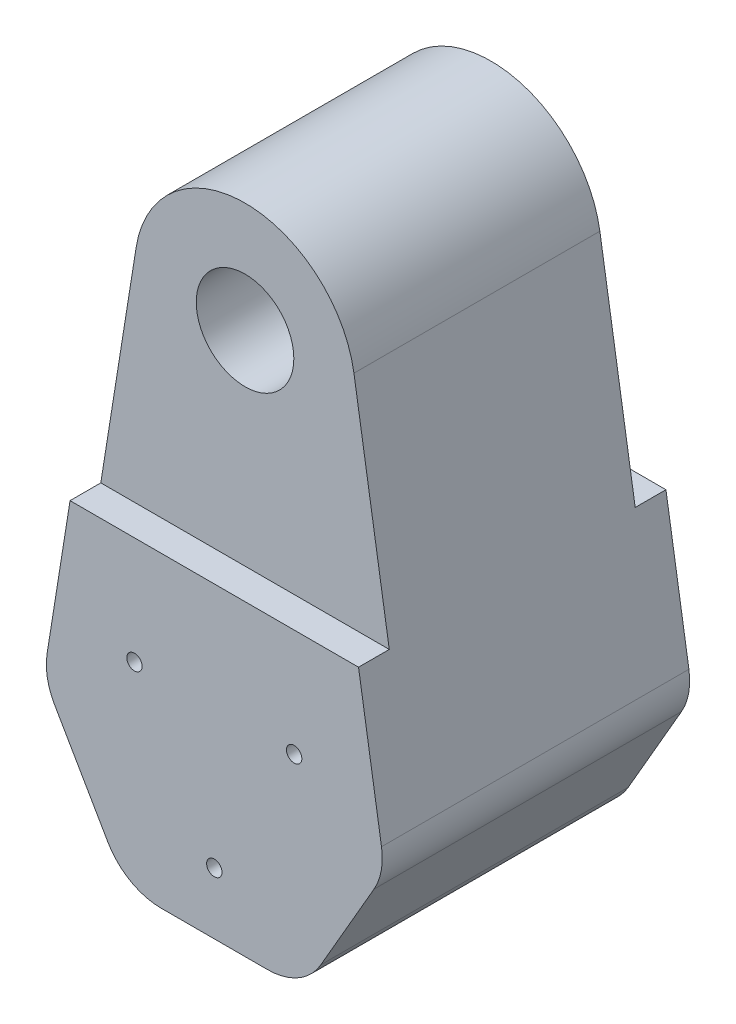
SolidWorks part; units mm, degrees
material "6061-T6 (SS)"
ref_plane "Front Plane" through (0, 0, 0) normal (0, 0, 1) x (1, 0, 0)
ref_plane "Top Plane" through (0, 0, 0) normal (0, 1, 0) x (1, 0, 0)
ref_plane "Right Plane" through (0, 0, 0) normal (1, 0, 0) x (0, 0, -1)
sketch "Sketch1" plane through (0, 0, 0) normal (0, 0, 1) x (1, 0, 0)
  line L0 (-17.7137, 2.8246) -> (-27.1957, -56.6385)
  line L1 (-25.9808, -63.2132) -> (-17.3205, -78.2132)
  line L2 (-8.6603, -83.2132) -> (8.6603, -83.2132)
  line L3 (17.3205, -78.2132) -> (25.9808, -63.2132)
  line L4 (27.1957, -56.6385) -> (17.7137, 2.8246)
  line L11 (105.7091, -33.2132) -> (-105.7091, -33.2132) construction
  line L12 (-93.4741, -83.2132) -> (93.4741, -83.2132) construction
  line L13 (0, -58.2132) -> (21.6506, -70.7132) construction
  line L14 (-23.4603, -33.2132) -> (23.4603, -33.2132)
  circle A0 centre (0, 0) radius 7.9375
  arc A1 (-17.7137, 2.8246) -> (17.7137, 2.8246) centre (0, 0) cw
  circle A2 centre (0, -58.2132) radius 15 construction
  circle A3 centre (-12.9904, -50.7132) radius 1.25
  circle A4 centre (12.9904, -50.7132) radius 1.25
  circle A5 centre (0, -73.2132) radius 1.25
  arc A8 (25.9808, -63.2132) -> (27.1957, -56.6385) centre (17.3205, -58.2132) ccw
  arc A9 (8.6603, -83.2132) -> (17.3205, -78.2132) centre (8.6603, -73.2132) ccw
  arc A10 (-17.3205, -78.2132) -> (-8.6603, -83.2132) centre (-8.6603, -73.2132) ccw
  arc A11 (-27.1957, -56.6385) -> (-25.9808, -63.2132) centre (-17.3205, -58.2132) ccw
  circle A12 centre (0, -58.2132) radius 15 construction
  circle A13 centre (-12.9904, -50.7132) radius 1.65 construction
  point P11 (0, -83.2132)
  point P20 (0, -58.2132)
  dimension "D1" = 15.875
  dimension "D4" = 2.5
  dimension "D8" = 10
  dimension "D11" = 10
  dimension "D3" = 3
extrude "Boss-Extrude1" add sketch "Sketch1" along normal mid plane 50 contours L0 A11 L1 A10 L2 A9 L3 A8 L4 L14 A3 A4 A5 region at (0, -56.6086, 0)
extrude "Boss-Extrude2" add sketch "Sketch1<3>" along normal mid plane 40 contours A1 L0 L14 L4 A0 region at (0, -11.8814, 0)
sketch "Sketch1<3>" plane through (0, 0, 0) normal (0, 0, 1) x (1, 0, 0) same geometry as "Sketch1"
